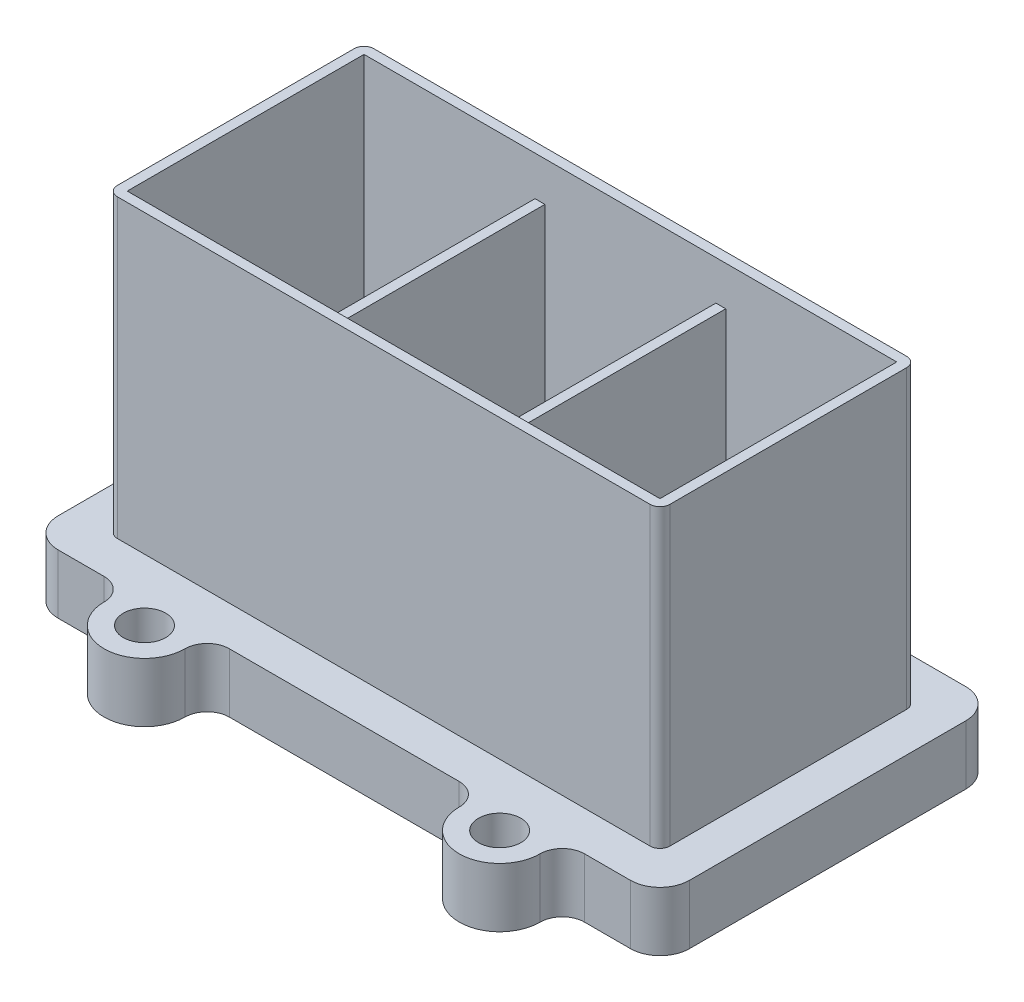
SolidWorks part; units mm, degrees
ref_plane "Front Plane" through (0, 0, 0) normal (0, 0, 1) x (1, 0, 0)
ref_plane "Top Plane" through (0, 0, 0) normal (0, 1, 0) x (1, 0, 0)
ref_plane "Right Plane" through (0, 0, 0) normal (1, 0, 0) x (0, 0, -1)
sketch "Base-plate and ports" plane through (0, 0, 0) normal (0, 1, 0) x (1, 0, 0)
  line L5 (-16, -7) -> (-16, 7)
  line L10 (-15, -7) -> (-15, 7)
  line L11 (-14.5, 7.5) -> (14.5, 7.5)
  line L12 (15, -7) -> (15, 7)
  line L13 (-14.5, -7.5) -> (14.5, -7.5)
  line L14 (16, -7) -> (16, 7)
  line L16 (-14.5, -8.5) -> (14.5, -8.5) construction
  line L17 (-14.5, 8.5) -> (14.5, 8.5) construction
  line L18 (-14.5, 8.5) -> (-3.175, 8.5)
  line L20 (3.175, 8.5) -> (14.5, 8.5)
  line L21 (12.175, -8.5) -> (14.5, -8.5)
  line L22 (5.825, -8.5) -> (-5.825, -8.5)
  line L23 (-12.175, -8.5) -> (-14.5, -8.5)
  circle A33 centre (-10.5, 3) radius 0.35
  circle A34 centre (0, 3) radius 0.35
  circle A35 centre (10.5, 3) radius 0.35
  circle A36 centre (0, -3) radius 0.35
  circle A37 centre (10.5, -3) radius 0.35
  circle A38 centre (-10.5, -3) radius 0.35
  arc A41 (-15, -7) -> (-14.5, -7.5) centre (-14.5, -7) ccw
  arc A42 (14.5, -7.5) -> (15, -7) centre (14.5, -7) ccw
  arc A43 (15, 7) -> (14.5, 7.5) centre (14.5, 7) ccw
  arc A44 (-14.5, 7.5) -> (-15, 7) centre (-14.5, 7) ccw
  circle A45 centre (0, 9.625) radius 1.075
  circle A46 centre (-9, -9.625) radius 1.075
  circle A47 centre (9, -9.625) radius 1.075
  arc A48 (-14.5, 8.5) -> (-16, 7) centre (-14.5, 7) ccw
  arc A49 (16, 7) -> (14.5, 8.5) centre (14.5, 7) ccw
  arc A50 (14.5, -8.5) -> (16, -7) centre (14.5, -7) ccw
  arc A51 (-16, -7) -> (-14.5, -8.5) centre (-14.5, -7) ccw
  arc A52 (-11.05, -9.625) -> (-6.95, -9.625) centre (-9, -9.625) ccw
  arc A53 (6.95, -9.625) -> (11.05, -9.625) centre (9, -9.625) ccw
  arc A54 (-2.05, 9.625) -> (2.05, 9.625) centre (0, 9.625) cw
  arc A55 (-11.05, -9.625) -> (-12.175, -8.5) centre (-12.175, -9.625) ccw
  arc A56 (-6.95, -9.625) -> (-5.825, -8.5) centre (-5.825, -9.625) cw
  arc A57 (6.95, -9.625) -> (5.825, -8.5) centre (5.825, -9.625) ccw
  arc A58 (11.05, -9.625) -> (12.175, -8.5) centre (12.175, -9.625) cw
  arc A59 (2.05, 9.625) -> (3.175, 8.5) centre (3.175, 9.625) ccw
  arc A60 (-2.05, 9.625) -> (-3.175, 8.5) centre (-3.175, 9.625) cw
  point P2 (-15, -7.5)
  point P5 (0, 7.5)
  point P10 (15, 7.5)
  point P16 (-15, 7.5)
  point P17 (-15, 0)
  dimension "D7" = 30
  dimension "D3" = 6
  dimension "D8" = 10.5
  dimension "D9" = 0.5
  dimension "D10" = 0.7
  dimension "D18" = 1
  dimension "D19" = 4.1
  dimension "D5" = 4.5
  dimension "D12" = 2.125
  dimension "D13" = 2.125
  dimension "D11" = 2.15
  dimension "D2" = 4.5
  dimension "D6" = 10.5
  dimension "D4" = 15
  dimension "D16" = 2
  dimension "D17" = 18
  dimension "D14" = 6
  dimension "D15" = 3
extrude "Base plate and ports" add sketch "Base-plate and ports" along normal mid plane 3 contours L13 L10 L11 L12 | L10 L13 L12 L11 A38 A37 A36 A35 A34 A33 region at (-15.6039, 0, 0) region at (0, 0, 0)
sketch "Reservoirs" plane through (0, 1.5, 0) normal (0, 1, 0) x (1, 0, 0)
  line L0 (-15, -7) -> (-15, 7) construction
  line L1 (-13.5, -6.5) -> (13.5, -6.5)
  line L2 (-14, -6) -> (-14, 6)
  line L3 (-13.5, 6.5) -> (13.5, 6.5)
  line L4 (14, -6) -> (14, 6)
  line L5 (-14, -6.5) -> (14, 6.5) construction
  line L6 (-14, 6.5) -> (14, -6.5) construction
  line L7 (-14.5, 7.5) -> (14.5, 7.5) construction
  line L8 (-4.3333, -6) -> (4.3333, -6)
  line L9 (-13.5, -6) -> (-4.8333, -6)
  line L10 (-13.5, -6) -> (-13.5, 6)
  line L11 (-13.5, 6) -> (-4.8333, 6)
  line L12 (-4.8333, -6) -> (-4.8333, 6)
  line L13 (-13.5, -6) -> (-4.8333, 6) construction
  line L14 (-13.5, 6) -> (-4.8333, -6) construction
  line L15 (-4.3333, -6) -> (-4.3333, 6)
  line L16 (-4.3333, 6) -> (4.3333, 6)
  line L17 (4.3333, -6) -> (4.3333, 6)
  line L18 (-4.3333, -6) -> (4.3333, 6) construction
  line L19 (-4.3333, 6) -> (4.3333, -6) construction
  line L20 (4.8333, -6) -> (13.5, -6)
  line L21 (4.8333, -6) -> (4.8333, 6)
  line L22 (4.8333, 6) -> (13.5, 6)
  line L23 (13.5, -6) -> (13.5, 6)
  line L24 (4.8333, -6) -> (13.5, 6) construction
  line L25 (4.8333, 6) -> (13.5, -6) construction
  line L26 (-4.8333, 6) -> (-4.3333, 6)
  line L27 (4.3333, 6) -> (4.8333, 6)
  line L28 (4.8333, -6) -> (4.3333, -6)
  line L29 (-4.3333, -6) -> (-4.8333, -6)
  arc A0 (-14, -6) -> (-13.5, -6.5) centre (-13.5, -6) ccw
  arc A1 (13.5, -6.5) -> (14, -6) centre (13.5, -6) ccw
  arc A2 (14, 6) -> (13.5, 6.5) centre (13.5, 6) ccw
  arc A3 (-13.5, 6.5) -> (-14, 6) centre (-13.5, 6) ccw
  point P0 (0, 0)
  point P10 (-9.1667, 0)
  point P16 (9.1667, 0)
  point P18 (0, 0)
  dimension "D10" = 0.5
  dimension "D1" = 1
  dimension "D2" = 1
  dimension "D3" = 0.5
  dimension "D4" = 0.5
  dimension "D5" = 0.5
  dimension "D6" = 0.5
  dimension "D7" = 0.5
  dimension "D8" = 0.5
  dimension "D9" = 0.5
extrude "Boss-Extrude1" add sketch "Reservoirs" along normal blind 15 contours L3 A3 L2 A0 L1 A1 L4 A2 L8 L29 L9 L10 L11 L26 L16 L27 L22 L23 L20 L28 region at (-13.6353, 1.5, 6.1353)
extrude "Boss-Extrude2" add sketch "Reservoirs<3>" along normal offset from surface (13 mm away) 2 contours L29 L15 L26 L12 | L28 L21 L27 L17 region at (-4.5833, 1.5, 0) region at (4.5833, 1.5, 0) up to face at (0, 16.5, 0)
sketch "Reservoirs<3>" plane through (0, 1.5, 0) normal (0, 1, 0) x (1, 0, 0) same geometry as "Reservoirs"
